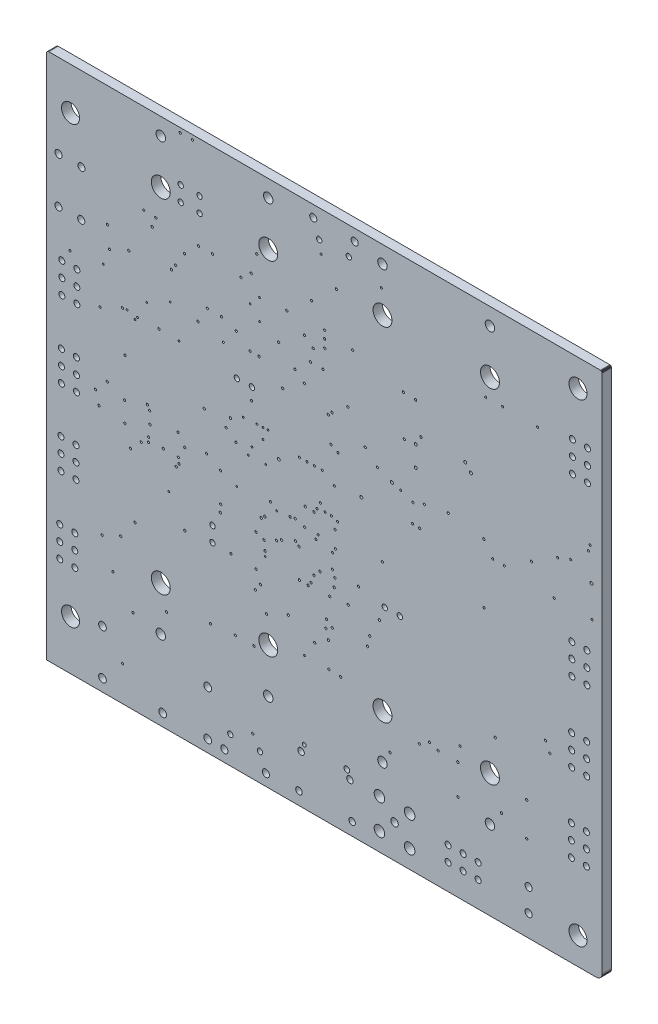
SolidWorks part; units mm, degrees
ref_plane "Front Plane" through (0, 0, 0) normal (0, 0, 1) x (1, 0, 0)
ref_plane "Top Plane" through (0, 0, 0) normal (0, 1, 0) x (1, 0, 0)
ref_plane "Right Plane" through (0, 0, 0) normal (1, 0, 0) x (0, 0, -1)
ref_plane "Dielectric_Layer Layer 1" through (0, 0, 1.6) normal (0, 0, 1) x (1, 0, 0)
sketch "Sketch1" plane through (0, 0, 0) normal (0, 0, 1) x (1, 0, 0)
  line L0 (-94.885, 89.2356) -> (-94.885, 0.5)
  line L1 (-94.885, 0.5) -> (-2.0072, 0.5)
  line L2 (-2.0072, 0.5) -> (-1.7465, 0.5343)
  line L3 (-1.7465, 0.5343) -> (-1.5036, 0.6349)
  line L4 (-1.5036, 0.6349) -> (-1.295, 0.795)
  line L5 (-1.295, 0.795) -> (-1.1349, 1.0036)
  line L6 (-1.1349, 1.0036) -> (-1.0343, 1.2465)
  line L7 (-1.0343, 1.2465) -> (-1, 1.5072)
  line L8 (-1, 1.5072) -> (-1, 89.3458)
  line L9 (-1, 89.3458) -> (-1.011, 89.4297)
  line L10 (-1.011, 89.4297) -> (-1.0434, 89.5079)
  line L11 (-1.0434, 89.5079) -> (-1.0949, 89.5751)
  line L12 (-1.0949, 89.5751) -> (-1.1621, 89.6266)
  line L13 (-1.1621, 89.6266) -> (-1.2403, 89.659)
  line L14 (-1.2403, 89.659) -> (-1.3242, 89.67)
  line L15 (-1.3242, 89.67) -> (-94.4506, 89.67)
  line L16 (-94.4506, 89.67) -> (-94.563, 89.6552)
  line L17 (-94.563, 89.6552) -> (-94.6678, 89.6118)
  line L18 (-94.6678, 89.6118) -> (-94.7578, 89.5428)
  line L19 (-94.7578, 89.5428) -> (-94.8268, 89.4528)
  line L20 (-94.8268, 89.4528) -> (-94.8702, 89.348)
  line L21 (-94.8702, 89.348) -> (-94.885, 89.2356)
extrude "Board_Outline" add sketch "Sketch1" along normal blind 1.6 separate body
sketch "Sketch2" plane through (0, 0, 0) normal (0, 0, 1) x (1, 0, 0)
  circle A0 centre (-51.3266, 9.8552) radius 0.325
  circle A1 centre (-44.1266, 9.8552) radius 0.475
  circle A2 centre (-19.9502, 21.4054) radius 1.6
  circle A3 centre (-38.1052, 21.4054) radius 1.6
  circle A4 centre (-57.4052, 21.4054) radius 1.6
  circle A5 centre (-19.9502, 79.3154) radius 1.6
  circle A6 centre (-75.5602, 21.4054) radius 1.6
  circle A7 centre (-75.5602, 79.3154) radius 1.6
  circle A8 centre (-38.1052, 79.3154) radius 1.6
  circle A9 centre (-57.4052, 79.3154) radius 1.6
  circle A10 centre (-59.5884, 28.3718) radius 0.1905
  circle A11 centre (-31.877, 19.7104) radius 0.1905
  circle A12 centre (-46.5582, 37.8968) radius 0.1905
  circle A13 centre (-57.8104, 47.5991) radius 0.15
  circle A14 centre (-49.1683, 45.466) radius 0.1905
  circle A15 centre (-38.9636, 56.6166) radius 0.1905
  circle A16 centre (-47.1678, 22.9616) radius 0.1905
  circle A17 centre (-47.5488, 30.099) radius 0.1905
  circle A18 centre (-36.83, 15.9512) radius 0.1905
  circle A19 centre (-46.8249, 56.0324) radius 0.1905
  circle A20 centre (-60.2742, 74.3458) radius 0.1905
  circle A21 centre (-55.6514, 66.5734) radius 0.1905
  circle A22 centre (-80.9752, 67.31) radius 0.1905
  circle A23 centre (-58.7069, 29.591) radius 0.1905
  circle A24 centre (-62.865, 48.3362) radius 0.1905
  circle A25 centre (-65.4812, 42.9006) radius 0.1905
  circle A26 centre (-55.9877, 41.7383) radius 0.15
  circle A27 centre (-57.912, 34.0868) radius 0.15
  circle A28 centre (-60.1472, 48.9924) radius 0.15
  circle A29 centre (-61.6148, 52.609) radius 0.15
  circle A30 centre (-17.8054, 76.073) radius 0.175
  circle A31 centre (-78.4352, 74.4982) radius 0.175
  circle A32 centre (-45.6184, 55.4228) radius 0.175
  circle A33 centre (-36.5252, 55.626) radius 0.25
  circle A34 centre (-55.626, 49.4792) radius 0.25
  circle A35 centre (-13.7414, 14.8844) radius 0.1905
  circle A36 centre (-13.7414, 20.574) radius 0.1905
  circle A37 centre (-43.1419, 71.6788) radius 0.1905
  circle A38 centre (-19.05, 27.051) radius 0.1905
  circle A39 centre (-32.4866, 59.7916) radius 0.25
  circle A40 centre (-48.6664, 36.5252) radius 0.1905
  circle A41 centre (-51.2499, 41.7249) radius 0.1905
  circle A42 centre (-54.9656, 60.1726) radius 0.1905
  circle A43 centre (-47.2694, 60.1726) radius 0.1905
  circle A44 centre (-49.3268, 40.894) radius 0.175
  circle A45 centre (-46.5582, 40.3352) radius 0.175
  circle A46 centre (-67.1576, 19.6342) radius 0.1905
  circle A47 centre (-49.5554, 25.654) radius 0.1905
  circle A48 centre (-46.5836, 29.3116) radius 0.1905
  circle A49 centre (-47.0154, 33.7058) radius 0.1905
  circle A50 centre (-49.6824, 35.4584) radius 0.1905
  circle A51 centre (-78.867, 40.3606) radius 0.1905
  circle A52 centre (-9.0932, 52.4256) radius 0.175
  circle A53 centre (-2.7178, 52.451) radius 0.175
  circle A54 centre (-72.4789, 40.3733) radius 0.1905
  circle A55 centre (-52.853, 42.1723) radius 0.1905
  circle A56 centre (-53.7083, 41.9989) radius 0.1905
  circle A57 centre (-72.9488, 39.7129) radius 0.1905
  circle A58 centre (-77.4087, 43.6702) radius 0.1905
  circle A59 centre (-86.0066, 42.1242) radius 0.1905
  circle A60 centre (-86.5976, 44.1802) radius 0.1905
  circle A61 centre (-75.8698, 58.42) radius 0.1905
  circle A62 centre (-73.0504, 69.1388) radius 0.1905
  circle A63 centre (-50.292, 66.3702) radius 0.1905
  circle A64 centre (-51.2826, 69.7738) radius 0.1905
  circle A65 centre (-80.6704, 38.5318) radius 0.1905
  circle A66 centre (-85.471, 23.4442) radius 0.1905
  circle A67 centre (-74.5998, 17.6276) radius 0.1905
  circle A68 centre (-24.9936, 22.8092) radius 0.1905
  circle A69 centre (-12.9286, 55.8546) radius 0.1905
  circle A70 centre (-27.0002, 55.9054) radius 0.1905
  circle A71 centre (-18.0086, 16.51) radius 0.1905
  circle A72 centre (-25.3492, 15.1892) radius 0.1905
  circle A73 centre (-57.9374, 34.8996) radius 0.1905
  circle A74 centre (-57.023, 42.545) radius 0.1905
  circle A75 centre (-52.1462, 33.528) radius 0.1905
  circle A76 centre (-43.8912, 34.036) radius 0.1905
  circle A77 centre (-40.259, 31.2928) radius 0.1905
  circle A78 centre (-40.64, 29.591) radius 0.1905
  circle A79 centre (-38.6334, 34.4424) radius 0.1905
  circle A80 centre (-42.1386, 37.592) radius 0.1905
  circle A81 centre (-65.4304, 37.973) radius 0.1905
  circle A82 centre (-65.5066, 36.7284) radius 0.1905
  circle A83 centre (-49.6697, 44.7294) radius 0.1905
  circle A84 centre (-60.0202, 7.1247) radius 0.1905
  circle A85 centre (-82.3214, 24.8412) radius 0.1905
  circle A86 centre (-81.5975, 51.7017) radius 0.1905
  circle A87 centre (-85.8139, 56.6293) radius 0.1905
  circle A88 centre (-85.2765, 63.1828) radius 0.15
  circle A89 centre (-84.2264, 65.8876) radius 0.1905
  circle A90 centre (-69.1896, 73.9013) radius 0.1905
  circle A91 centre (-66.8274, 73.9013) radius 0.1905
  circle A92 centre (-67.691, 65.5066) radius 0.1905
  circle A93 centre (-65.3161, 65.4812) radius 0.1905
  circle A94 centre (-62.8142, 64.6303) radius 0.1905
  circle A95 centre (-60.4774, 62.865) radius 0.1905
  circle A96 centre (-58.9534, 62.8523) radius 0.1905
  circle A97 centre (-32.512, 69.723) radius 0.1905
  circle A98 centre (-34.5694, 69.8119) radius 0.1905
  circle A99 centre (-47.879, 70.9549) radius 0.1905
  circle A100 centre (-47.879, 72.2249) radius 0.1905
  circle A101 centre (-47.8536, 69.5833) radius 0.1905
  circle A102 centre (-49.8094, 68.6181) radius 0.1905
  circle A103 centre (-58.8899, 71.5137) radius 0.15
  circle A104 centre (-58.8645, 67.9831) radius 0.15
  circle A105 centre (-60.4647, 69.7992) radius 0.15
  circle A106 centre (-59.3471, 77.6478) radius 0.1905
  circle A107 centre (-62.0268, 72.8853) radius 0.1905
  circle A108 centre (-41.021, 58.5343) radius 0.1905
  circle A109 centre (-52.8955, 64.008) radius 0.1905
  circle A110 centre (-51.308, 62.7253) radius 0.1905
  circle A111 centre (-67.818, 44.196) radius 0.1905
  circle A112 centre (-47.6758, 28.702) radius 0.1905
  circle A113 centre (-72.644, 44.9072) radius 0.1905
  circle A114 centre (-72.5932, 41.275) radius 0.1905
  circle A115 centre (-75.1332, 41.275) radius 0.1905
  circle A116 centre (-81.6864, 45.085) radius 0.1905
  circle A117 centre (-81.6356, 41.7068) radius 0.1905
  circle A118 centre (-76.4032, 74.422) radius 0.1905
  circle A119 centre (-45.8978, 79.2226) radius 0.1905
  circle A120 centre (-50.0888, 75.438) radius 0.1905
  circle A121 centre (-90.805, 82.55) radius 1.524
  circle A122 centre (-90.805, 8.89) radius 1.524
  circle A123 centre (-5.08, 5.08) radius 1.524
  circle A124 centre (-5.08, 85.09) radius 1.524
  circle A125 centre (-59.4614, 31.4706) radius 0.1905
  circle A126 centre (-63.7032, 31.5976) radius 0.1905
  circle A127 centre (-57.7088, 25.8064) radius 0.1905
  circle A128 centre (-54.0258, 27.4828) radius 0.1905
  circle A129 centre (-60.2234, 55.7276) radius 0.1905
  circle A130 centre (-63.8048, 51.4096) radius 0.1905
  circle A131 centre (-64.516, 49.6316) radius 0.1905
  circle A132 centre (-79.4849, 58.2847) radius 0.15
  circle A133 centre (-81.2697, 58.5147) radius 0.15
  circle A134 centre (-73.9648, 63.2968) radius 0.15
  circle A135 centre (-74.1934, 35.4584) radius 0.15
  circle A136 centre (-58.293, 51.0286) radius 0.15
  circle A137 centre (-57.4548, 52.832) radius 0.15
  circle A138 centre (-59.309, 52.7558) radius 0.15
  circle A139 centre (-58.293, 52.7812) radius 0.15
  circle A140 centre (-51.2826, 22.9362) radius 0.15
  circle A141 centre (-60.7822, 47.498) radius 0.15
  circle A142 centre (-62.7126, 41.9354) radius 0.15
  circle A143 centre (-77.9272, 61.2394) radius 0.15
  circle A144 centre (-72.2757, 88.9) radius 0.1905
  circle A145 centre (-70.2183, 88.9) radius 0.1905
  circle A146 centre (-48.4632, 83.0326) radius 0.175
  circle A147 centre (-68.2244, 50.5714) radius 0.2
  circle A148 centre (-3.0226, 63.2206) radius 0.175
  circle A149 centre (-11.9126, 76.0222) radius 0.175
  circle A150 centre (-2.794, 57.7342) radius 0.25
  circle A151 centre (-32.4866, 63.2206) radius 0.25
  circle A152 centre (-23.1648, 63.7032) radius 0.25
  circle A153 centre (-41.6814, 50.8762) radius 0.25
  circle A154 centre (-71.5518, 71.5772) radius 0.1905
  circle A155 centre (-69.2912, 62.7888) radius 0.1905
  circle A156 centre (-46.0502, 41.148) radius 0.1905
  circle A157 centre (-48.9712, 41.7322) radius 0.175
  circle A158 centre (-45.6946, 45.3136) radius 0.175
  circle A159 centre (-48.2854, 51.5366) radius 0.175
  circle A160 centre (-46.736, 45.6438) radius 0.175
  circle A161 centre (-49.6062, 51.5112) radius 0.175
  circle A162 centre (-47.8028, 45.6692) radius 0.175
  circle A163 centre (-50.8508, 51.4858) radius 0.175
  circle A164 centre (-48.5902, 46.5836) radius 0.175
  circle A165 centre (-52.1208, 51.4858) radius 0.175
  circle A166 centre (-57.9882, 39.9034) radius 0.1905
  circle A167 centre (-77.8256, 46.355) radius 0.1905
  circle A168 centre (-58.5978, 39.3954) radius 0.1905
  circle A169 centre (-77.4446, 45.6692) radius 0.1905
  circle A170 centre (-55.1434, 37.8968) radius 0.1905
  circle A171 centre (-8.509, 58.6232) radius 0.175
  circle A172 centre (-56.007, 37.4015) radius 0.1905
  circle A173 centre (-6.2992, 59.4614) radius 0.175
  circle A174 centre (-59.4614, 36.9062) radius 0.1905
  circle A175 centre (-77.6371, 40.9448) radius 0.1905
  circle A176 centre (-58.1406, 36.3982) radius 0.1905
  circle A177 centre (-77.6224, 41.7068) radius 0.1905
  circle A178 centre (-46.1518, 36.8554) radius 0.1905
  circle A179 centre (-84.6074, 46.3296) radius 0.1905
  circle A180 centre (-79.9084, 57.7596) radius 0.15
  circle A181 centre (-82.0166, 58.3946) radius 0.1905
  circle A182 centre (-38.3032, 83.2104) radius 0.175
  circle A183 centre (-71.5137, 31.0896) radius 0.1905
  circle A184 centre (-46.2534, 35.4076) radius 0.1905
  circle A185 centre (-30.1752, 20.7899) radius 0.1905
  circle A186 centre (-28.702, 20.2946) radius 0.1905
  circle A187 centre (-25.3746, 20.2946) radius 0.1905
  circle A188 centre (-9.8298, 29.337) radius 0.1905
  circle A189 centre (-52.2224, 38.4175) radius 0.1905
  circle A190 centre (-52.8066, 38.9382) radius 0.1905
  circle A191 centre (-10.5664, 30.861) radius 0.1905
  circle A192 centre (-35.0266, 55.2196) radius 0.175
  circle A193 centre (-46.1264, 43.942) radius 0.175
  circle A194 centre (-33.02, 51.3334) radius 0.1905
  circle A195 centre (-32.9692, 54.4957) radius 0.1905
  circle A196 centre (-31.8262, 51.2572) radius 0.1905
  circle A197 centre (-31.0388, 55.1688) radius 0.1905
  circle A198 centre (-20.9804, 55.118) radius 0.1905
  circle A199 centre (-20.955, 45.085) radius 0.1905
  circle A200 centre (-38.1308, 43.2235) radius 0.1905
  circle A201 centre (-51.1603, 44.7929) radius 0.1905
  circle A202 centre (-20.6756, 75.9968) radius 0.175
  circle A203 centre (-46.2534, 50.2666) radius 0.175
  circle A204 centre (-19.4818, 52.959) radius 0.175
  circle A205 centre (-17.526, 52.959) radius 0.175
  circle A206 centre (-50.673, 33.5026) radius 0.1905
  circle A207 centre (-47.244, 27.2034) radius 0.1905
  circle A208 centre (-50.165, 34.1376) radius 0.1905
  circle A209 centre (-45.1739, 22.8473) radius 0.1905
  circle A210 centre (-82.0166, 6.3754) radius 0.1905
  circle A211 centre (-71.501, 43.2562) radius 0.1905
  circle A212 centre (-77.0128, 72.771) radius 0.1905
  circle A213 centre (-54.2798, 71.882) radius 0.1905
  circle A214 centre (-46.6344, 60.8076) radius 0.1905
  circle A215 centre (-31.5976, 64.7192) radius 0.1905
  circle A216 centre (-72.4916, 58.3438) radius 0.15
  circle A217 centre (-3.3274, 62.23) radius 0.175
  circle A218 centre (-24.13, 64.7954) radius 0.25
  circle A219 centre (-84.582, 69.3166) radius 0.1905
  circle A220 centre (-62.9666, 20.0406) radius 0.1905
  circle A221 centre (-59.817, 20.0406) radius 0.1905
  circle A222 centre (-80.2386, 14.7066) radius 0.1905
  circle A223 centre (-83.6422, 18.9992) radius 0.1905
  circle A224 centre (-79.9084, 28.067) radius 0.1905
  circle A225 centre (-73.7616, 68.1482) radius 0.1905
  circle A226 centre (-48.1584, 66.3702) radius 0.1905
  circle A227 centre (-90.9066, 62.3316) radius 0.1905
  circle A228 centre (-43.9674, 62.9666) radius 0.1905
  circle A229 centre (-34.4297, 63.0047) radius 0.1905
  circle A230 centre (-64.9986, 61.9252) radius 0.175
extrude "NPTH" cut sketch "Sketch2" along normal through all
sketch "Sketch3" plane through (0, 0, 0) normal (0, 0, 1) x (1, 0, 0)
  circle A0 centre (-63.81, 5.14) radius 0.45
  circle A1 centre (-58.81, 5.14) radius 0.45
  circle A2 centre (-64.81, 2.44) radius 0.6
  circle A3 centre (-57.81, 2.44) radius 0.6
  circle A4 centre (-51.86, 8.61) radius 0.55
  circle A5 centre (-43.6, 8.61) radius 0.55
  circle A6 centre (-52.22, 2.66) radius 0.55
  circle A7 centre (-43.24, 2.66) radius 0.55
  circle A8 centre (-36.07, 6.13) radius 0.635
  circle A9 centre (-38.62, 8.68) radius 0.89
  circle A10 centre (-33.52, 8.68) radius 0.89
  circle A11 centre (-33.52, 3.58) radius 0.89
  circle A12 centre (-38.62, 3.58) radius 0.89
  circle A13 centre (-19.95, 13.91) radius 0.8
  circle A14 centre (-38.11, 13.91) radius 0.8
  circle A15 centre (-57.41, 13.91) radius 0.8
  circle A16 centre (-75.56, 13.91) radius 0.8
  circle A17 centre (-75.56, 86.81) radius 0.8
  circle A18 centre (-57.41, 86.81) radius 0.8
  circle A19 centre (-38.11, 86.81) radius 0.8
  circle A20 centre (-19.95, 86.81) radius 0.8
  circle A21 centre (-92.28, 60.22) radius 0.51
  circle A22 centre (-89.74, 60.22) radius 0.51
  circle A23 centre (-92.28, 57.68) radius 0.51
  circle A24 centre (-89.74, 57.68) radius 0.51
  circle A25 centre (-92.28, 55.14) radius 0.51
  circle A26 centre (-89.74, 55.14) radius 0.51
  circle A27 centre (-92.35, 47.29) radius 0.51
  circle A28 centre (-89.81, 47.29) radius 0.51
  circle A29 centre (-92.35, 44.75) radius 0.51
  circle A30 centre (-89.81, 44.75) radius 0.51
  circle A31 centre (-92.35, 42.21) radius 0.51
  circle A32 centre (-89.81, 42.21) radius 0.51
  circle A33 centre (-3.58, 42.47) radius 0.51
  circle A34 centre (-6.12, 42.47) radius 0.51
  circle A35 centre (-3.58, 45.01) radius 0.51
  circle A36 centre (-6.12, 45.01) radius 0.51
  circle A37 centre (-3.58, 47.55) radius 0.51
  circle A38 centre (-6.12, 47.55) radius 0.51
  circle A39 centre (-3.61, 29.13) radius 0.51
  circle A40 centre (-6.15, 29.13) radius 0.51
  circle A41 centre (-3.61, 31.67) radius 0.51
  circle A42 centre (-6.15, 31.67) radius 0.51
  circle A43 centre (-3.61, 34.21) radius 0.51
  circle A44 centre (-6.15, 34.21) radius 0.51
  circle A45 centre (-92.43, 34.44) radius 0.51
  circle A46 centre (-89.89, 34.44) radius 0.51
  circle A47 centre (-92.43, 31.9) radius 0.51
  circle A48 centre (-89.89, 31.9) radius 0.51
  circle A49 centre (-92.43, 29.36) radius 0.51
  circle A50 centre (-89.89, 29.36) radius 0.51
  circle A51 centre (-92.63, 21.46) radius 0.51
  circle A52 centre (-90.09, 21.46) radius 0.51
  circle A53 centre (-92.63, 18.92) radius 0.51
  circle A54 centre (-90.09, 18.92) radius 0.51
  circle A55 centre (-92.63, 16.38) radius 0.51
  circle A56 centre (-90.09, 16.38) radius 0.51
  circle A57 centre (-27.03, 4.8) radius 0.51
  circle A58 centre (-27.03, 7.34) radius 0.51
  circle A59 centre (-24.49, 4.8) radius 0.51
  circle A60 centre (-24.49, 7.34) radius 0.51
  circle A61 centre (-21.95, 4.8) radius 0.51
  circle A62 centre (-21.95, 7.34) radius 0.51
  circle A63 centre (-3.66, 15.9) radius 0.51
  circle A64 centre (-6.2, 15.9) radius 0.51
  circle A65 centre (-3.66, 18.44) radius 0.51
  circle A66 centre (-6.2, 18.44) radius 0.51
  circle A67 centre (-3.66, 20.98) radius 0.51
  circle A68 centre (-6.2, 20.98) radius 0.51
  circle A69 centre (-92.83, 75.55) radius 0.6
  circle A70 centre (-88.97, 75.55) radius 0.6
  circle A71 centre (-89, 67.82) radius 0.6
  circle A72 centre (-92.86, 67.82) radius 0.6
  circle A73 centre (-13.42, 8.01) radius 0.6
  circle A74 centre (-13.42, 4.15) radius 0.6
  circle A75 centre (-43.8, 85.03) radius 0.45
  circle A76 centre (-48.8, 85.03) radius 0.45
  circle A77 centre (-42.8, 87.73) radius 0.6
  circle A78 centre (-49.8, 87.73) radius 0.6
  circle A79 centre (-3.48, 72.11) radius 0.51
  circle A80 centre (-6.02, 72.11) radius 0.51
  circle A81 centre (-3.48, 74.65) radius 0.51
  circle A82 centre (-6.02, 74.65) radius 0.51
  circle A83 centre (-3.48, 77.19) radius 0.51
  circle A84 centre (-6.02, 77.19) radius 0.51
  circle A85 centre (-66.83, 34.19) radius 0.455
  circle A86 centre (-66.83, 31.65) radius 0.455
  circle A87 centre (-37.72, 36.75) radius 0.455
  circle A88 centre (-35.18, 36.75) radius 0.455
  circle A89 centre (-69.01, 81.31) radius 0.455
  circle A90 centre (-69.01, 78.77) radius 0.455
  circle A91 centre (-72.2, 81.32) radius 0.455
  circle A92 centre (-72.2, 78.78) radius 0.455
  circle A93 centre (-60.17, 57.76) radius 0.455
  circle A94 centre (-62.71, 57.76) radius 0.455
  circle A95 centre (-85.41, 2.54) radius 0.65
  circle A96 centre (-85.41, 10.16) radius 0.65
  circle A97 centre (-75.25, 2.54) radius 0.65
  circle A98 centre (-67.63, 10.16) radius 0.65
  circle A99 centre (-67.63, 2.54) radius 0.65
extrude "PTH" cut sketch "Sketch3" along normal through all
